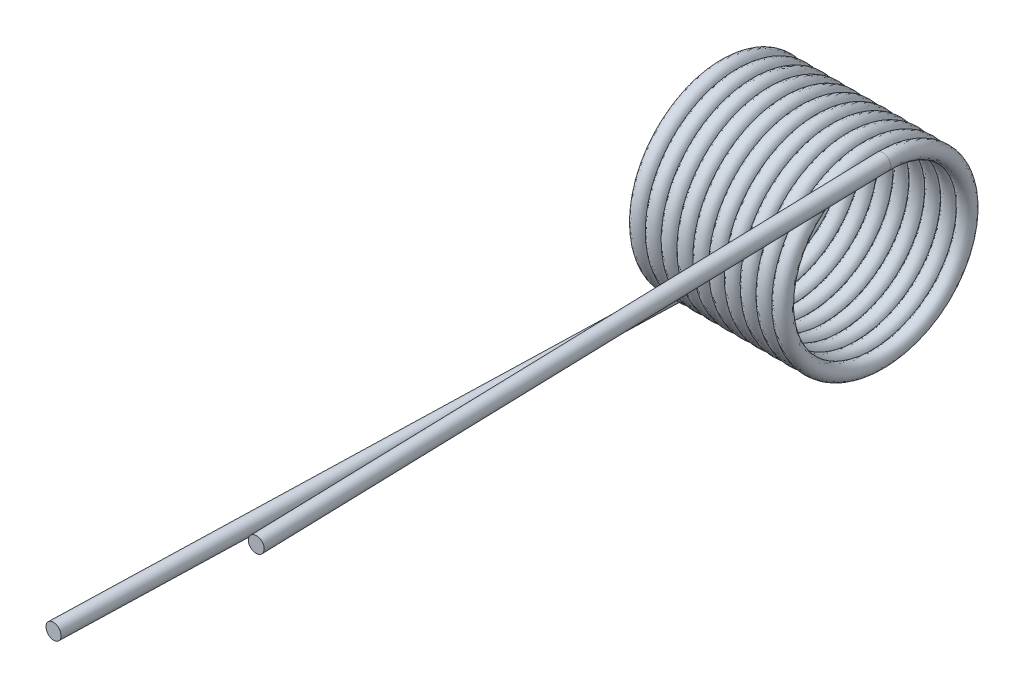
SolidWorks part; units mm, degrees
ref_plane "Front" through (0, 0, 0) normal (0, 0, 1) x (1, 0, 0)
ref_plane "Top" through (0, 0, 0) normal (0, 1, 0) x (1, 0, 0)
ref_plane "Right" through (0, 0, 0) normal (1, 0, 0) x (0, 0, -1)
sketch "Sketch1" plane through (0, 0, 0) normal (1, 0, 0) x (0, 0, -1)
  line L0 (0, -6.3373) -> (0, -7.5565) construction
  line L1 (0, 7.5565) -> (-50.8, 7.5565) construction
  line L2 (0, -7.5565) -> (-50.8, -7.5565) construction
  line L3 (0, 0) -> (7.5565, 0) construction
  line L4 (0, 0) -> (0, 7.5565) construction
  line L5 (-50.8, -7.5565) -> (-50.8, -6.3373) construction
  line L6 (-50.8, -6.3373) -> (0, -6.3373) construction
  line L7 (-50.8, 7.5565) -> (-50.8, 6.3373) construction
  line L8 (-50.8, 6.3373) -> (0, 6.3373) construction
  circle A0 centre (0, 0) radius 7.5565 construction
  circle A1 centre (0, 0) radius 4.953 construction
  circle A2 centre (0, 0) radius 6.9469 construction
  point P7 (0, -6.9469)
  point P10 (0, 7.5565)
  dimension "OD" = 15.113
  dimension "For Shaft Diameter" = 9.906
  dimension "Wire Diameter" = 1.2192
  dimension "Leg Length" = 50.8
  dimension "Deflection Angle" = 360
sketch "Sketch2" plane through (0, 0, 0) normal (1, 0, 0) x (0, 0, -1)
  circle A0 centre (0, 0) radius 6.9469 construction
  circle A2 centre (0, 0) radius 6.9469
curve "Helix/Spiral1" pitch 1.2446 height 13.0683 radius 6.9469 centre (0, 0, 0) axis (1, 0, 0) start towards (0, 0, -1)
ref_plane "Plane1" through (0, -6.9469, 0) normal (0.0285, 0, -0.9996) x (0.9993, -0.0232, 0.0285)
sketch "Sketch3" plane through (0, -6.9469, 0) normal (0.0285, 0, -0.9996) x (0.9993, -0.0232, 0.0285)
  circle A0 centre (0, 0) radius 0.6096
  dimension "D1" = 1.2192
sweep "Sweep1" add profiles "Sketch3" path "Helix/Spiral1"
sketch "Sketch4" plane through (0, 0, 0) normal (-0.0285, 0, 0.9996) x (-0.9993, 0.0232, -0.0285)
  circle A1 centre (-0.1614, 6.945) radius 0.6096
  circle A2 centre (-0.1614, 6.945) radius 0.6096
  dimension "D1" = 0
extrude "Extrude1" add sketch "Sketch4" along normal blind 50.8
sketch "Sketch5" plane through (0.0106, 0, 0.3723) normal (0.0285, 0, 0.9996) x (0.9984, -0.0482, -0.0285)
  circle A1 centre (12.713, 7.5684) radius 0.6096
  circle A2 centre (12.713, 7.5684) radius 0.6096
  dimension "D1" = 0
extrude "Extrude2" add sketch "Sketch5" along normal blind 50.8
sketch "Sketch6" plane through (0, 0, 0) normal (1, 0, 0) x (0, 0, -1)
  circle A2 centre (0, 0) radius 6.3373 construction
equation "\"D4@Helix/Spiral1\" = \"Wire Diameter@Sketch1\" + .001"
equation "\"D1@Sketch3\"=\"Wire Diameter@Sketch1\""
equation "\"D1@Extrude2\"=\"Leg Length@Sketch1\""
equation "\"Leg Length@Extrude1\"=\"Leg Length@Sketch1\""
